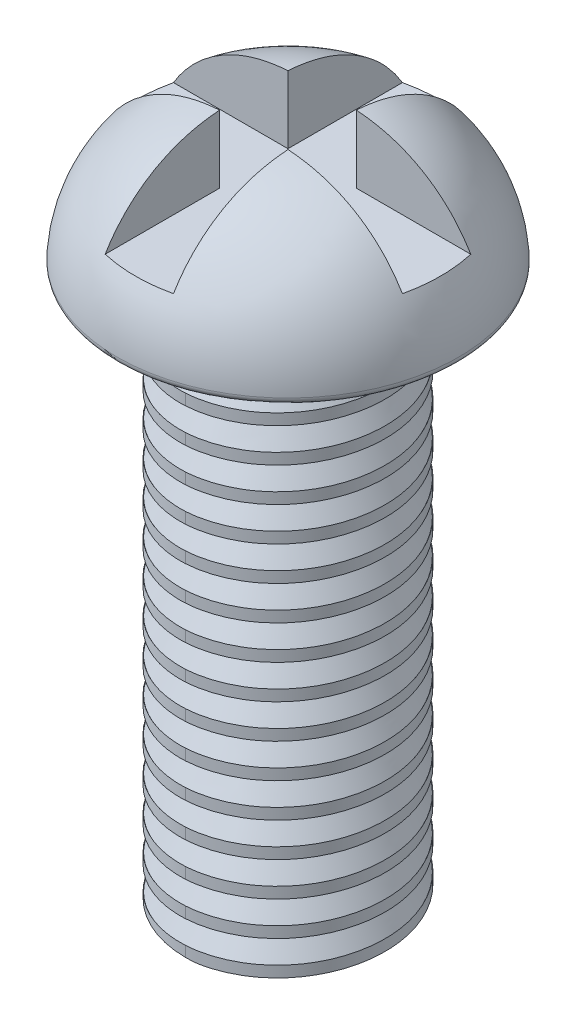
SolidWorks part; units mm, degrees
ref_plane "前视基准面" through (0, 0, 0) normal (0, 0, 1) x (1, 0, 0)
ref_plane "上视基准面" through (0, 0, 0) normal (0, 1, 0) x (1, 0, 0)
ref_plane "右视基准面" through (0, 0, 0) normal (1, 0, 0) x (0, 0, -1)
sketch "草图1" plane through (0, 0, 0) normal (0, 1, 0) x (1, 0, 0)
  circle A0 centre (0, 0) radius 1.5
  dimension "D1" = 3
extrude "凸台-拉伸1" add sketch "草图1" against normal blind 8
sketch "草图2" plane through (0, 0, 0) normal (0, 1, 0) x (1, 0, 0)
  circle A0 centre (0, 0) radius 2.5
  dimension "D1" = 5
extrude "凸台-拉伸2" add sketch "草图2" along normal blind 2
fillet "圆角1" radius 2 1 edges at (0, 2, 2.5)
sketch "草图3" plane through (0, 2, 0) normal (0, 1, 0) x (1, 0, 0)
  line L0 (2.5, 0.5) -> (-2.5, 0.5)
  line L1 (-0.5, 2.5) -> (0.5, 2.5)
  line L2 (-0.5, 2.5) -> (-0.5, -2.5)
  line L3 (-0.5, -2.5) -> (0.5, -2.5)
  line L4 (0.5, 2.5) -> (0.5, -2.5)
  line L5 (-0.5, 2.5) -> (0.5, -2.5) construction
  line L6 (-0.5, -2.5) -> (0.5, 2.5) construction
  line L7 (2.5, 0.5) -> (2.5, -0.5)
  line L8 (2.5, -0.5) -> (-2.5, -0.5)
  line L9 (-2.5, 0.5) -> (-2.5, -0.5)
  circle A0 centre (0, 0) radius 0.5 construction
  circle A1 centre (0, 0) radius 2.5 construction
  point P0 (0, 0)
  point P6 (0.5, 0)
  point P9 (-0.5, 0)
  point P10 (0, -0.5)
  point P11 (0, 0.5)
  point P17 (0, 2.5)
  circle M9 centre (0, 0) radius 0.5
  dimension "D1" = 2
extrude "切除-拉伸1" cut sketch "草图3" against normal blind 1 contours L4 L1 L2 L0 | L8 L7 L0 L4 | L0 L9 L8 L2 | M9 | L4 L8 L2 L3 | L4 L0 M9 | L8 L4 M9 | L0 L2 M9 | L8 L2 M9 region at (1.5, 2, 0) region at (0.3883, 2, -0.3883) region at (0, 2, -1.5) region at (-0.3883, 2, -0.3883) region at (0, 2, 0) region at (0.3883, 2, 0.3883) region at (0, 2, 1.5) region at (-1.5, 2, 0) region at (-0.3883, 2, 0.3883)
fillet "圆角2" radius 0.1 1 edges at (0, 0, 2.5)
sketch "草图4" plane through (0, -8, 0) normal (0, -1, 0) x (1, 0, 0)
  circle A1 centre (0, 0) radius 1.5
curve "螺旋线/涡状线1" pitch 0.5 height 7.5 radius 1.5 centre (0, -8, 0) axis (0, 1, 0) start towards (1, 0, 0)
sketch "草图19" plane through (0, 0, 0) normal (0, 0, 1) x (1, 0, 0)
  line L1 (1.4947, -8.2309) -> (1.7026, -7.8892)
  line L2 (1.7026, -7.8892) -> (1.3027, -7.8799)
  line L3 (1.3027, -7.8799) -> (1.4947, -8.2309)
  circle A0 centre (1.5, -8) radius 0.1155 construction
  dimension "D1" = 0.4
sweep "切除-扫描3" cut profiles "草图19" path "螺旋线/涡状线1" align with end faces yes
